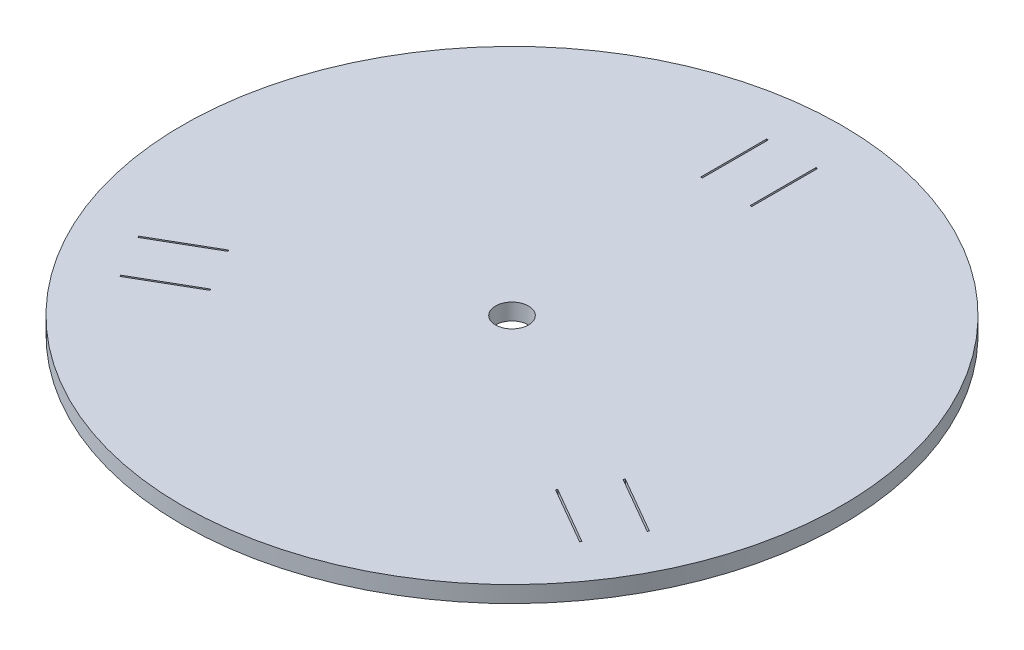
SolidWorks part; units mm, degrees
ref_plane "Front Plane" through (0, 0, 0) normal (0, 0, 1) x (1, 0, 0)
ref_plane "Top Plane" through (0, 0, 0) normal (0, 1, 0) x (1, 0, 0)
ref_plane "Right Plane" through (0, 0, 0) normal (1, 0, 0) x (0, 0, -1)
sketch "Sketch2" plane through (0, 0, 0) normal (0, 1, 0) x (1, 0, 0)
  circle A0 centre (0, 0) radius 100
  dimension "D1" = 200
extrude "Boss-Extrude1" add sketch "Sketch2" along normal blind 5
sketch "Sketch3" plane through (0, 5, 0) normal (0, 1, 0) x (1, 0, 0)
  line L0 (0, 0) -> (0, 100) construction
  line L1 (-7.5, 75) -> (7.5, 75) construction
  line L3 (-7.75, 65) -> (-7.25, 65)
  line L4 (-7.75, 65) -> (-7.75, 85)
  line L5 (-7.75, 85) -> (-7.25, 85)
  line L6 (-7.25, 65) -> (-7.25, 85)
  line L7 (-7.75, 65) -> (-7.25, 85) construction
  line L8 (-7.75, 85) -> (-7.25, 65) construction
  line L9 (7.25, 65) -> (7.75, 65)
  line L10 (7.25, 65) -> (7.25, 85)
  line L11 (7.25, 85) -> (7.75, 85)
  line L12 (7.75, 65) -> (7.75, 85)
  line L13 (7.25, 65) -> (7.75, 85) construction
  line L14 (7.25, 85) -> (7.75, 65) construction
  line L30 (60.1667, -25.7883) -> (77.4872, -35.7883)
  line L31 (60.1667, -25.7883) -> (59.9167, -26.2213)
  line L32 (59.9167, -26.2213) -> (77.2372, -36.2213)
  line L33 (77.4872, -35.7883) -> (77.2372, -36.2213)
  line L34 (52.6667, -38.7787) -> (69.9872, -48.7787)
  line L35 (52.6667, -38.7787) -> (52.4167, -39.2117)
  line L36 (52.4167, -39.2117) -> (69.7372, -49.2117)
  line L37 (69.9872, -48.7787) -> (69.7372, -49.2117)
  line L38 (-52.4167, -39.2117) -> (-69.7372, -49.2117)
  line L39 (-52.4167, -39.2117) -> (-52.6667, -38.7787)
  line L40 (-52.6667, -38.7787) -> (-69.9872, -48.7787)
  line L41 (-69.7372, -49.2117) -> (-69.9872, -48.7787)
  line L42 (-59.9167, -26.2213) -> (-77.2372, -36.2213)
  line L43 (-59.9167, -26.2213) -> (-60.1667, -25.7883)
  line L44 (-60.1667, -25.7883) -> (-77.4872, -35.7883)
  line L45 (-77.2372, -36.2213) -> (-77.4872, -35.7883)
  circle A0 centre (0, 0) radius 100 construction
  point P8 (0, 75)
  point P34 (0, 0)
  point P36 (0, 0)
  dimension "D1" = 15
  dimension "D2" = 20
  dimension "D3" = 0.5
  dimension "D4" = 75
  dimension "D5" = 3
extrude "Cut-Extrude1" cut sketch "Sketch3" against normal through all
sketch "Sketch4" plane through (0, 0, 0) normal (0, 0, 1) x (1, 0, 0)
  line L0 (-100, 0) -> (0, 0)
  line L1 (0, 0) -> (0, -31.5299)
  line L2 (0, -31.5299) -> (26.4846, -31.5299) construction
  line L3 (-100, 0) -> (-128.8281, 20.1856) construction
  arc A0 (0, -31.5299) -> (-100, 0) centre (0, 142.8148) cw
  dimension "D1" = 35
revolve "Revolve1" [suppressed] add sketch "Sketch4" angle 360 about L1
sketch "Sketch8" plane through (0, 0, 0) normal (0, -1, 0) x (-1, 0, 0)
  point P0 (0, 0)
hole_wizard "Ø10.0mm Dowel Hole1" positions "Sketch8" profile "Sketch7" hole size "Ø10.0" standard "ANSI Metric" end condition through all
sketch "Sketch7" plane through (0, 0, 0) normal (1, 0, 0) x (0, 0, -1)
  line L0 (0, 0) -> (0, 5)
  line L1 (0, 5) -> (5, 5)
  line L2 (5, 5) -> (5, 0.025)
  line L3 (5, 0.025) -> (5.025, 0)
  line L5 (5.025, 0) -> (0, 0)
  line L6 (-5, 0.025) -> (-5.025, 0) construction
  line L11 (0, -6.35) -> (0, 107.95) construction
  dimension "Thru Hole Dia." = 10
  dimension "Thru Hole Depth" = 5
  dimension "Near C'Sink Dia." = 10.05
  dimension "Near C'Sink Angle" = 90
equation "\"Leg_Spacing\"=40"
equation "\"Leaf_Spring_Slot_Width\"=5"
equation "\"Leaf_Spring_Thickness\"=0.2"
equation "\"Inner_Radius\"=75"
equation "\"Camera\"=120"
